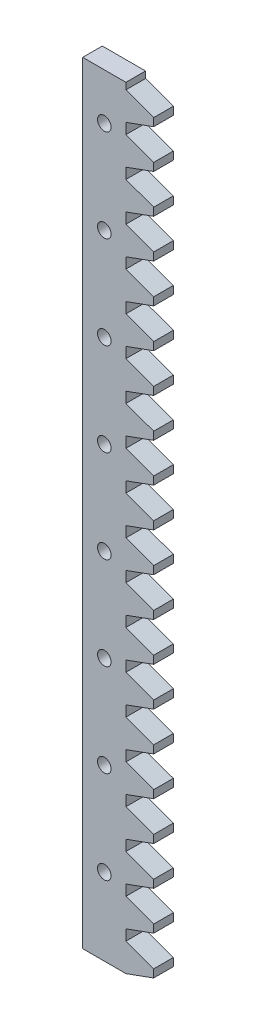
SolidWorks part; units mm, degrees
ref_plane "Front Plane" through (0, 0, 0) normal (0, 0, 1) x (1, 0, 0)
ref_plane "Top Plane" through (0, 0, 0) normal (0, 1, 0) x (1, 0, 0)
ref_plane "Right Plane" through (0, 0, 0) normal (1, 0, 0) x (0, 0, -1)
sketch "Sketch2" plane through (0, 0, 0) normal (0, 0, 1) x (1, 0, 0)
  line L0 (0, -62.5) -> (0, 62.5) construction
  line L1 (-3.5, -62.5) -> (3.5, -62.5) construction
  line L2 (-3.5, -62.5) -> (-3.5, 62.5) construction
  line L3 (-3.5, 62.5) -> (3.5, 62.5) construction
  line L4 (3.5, -62.5) -> (3.5, 62.5) construction
  line L5 (-3.5, -62.5) -> (3.5, 62.5) construction
  line L6 (-3.5, 62.5) -> (3.5, -62.5) construction
  line L8 (5.5085, -61.769) -> (8, -60.8621)
  line L9 (8, -60.8621) -> (8, -59.5784)
  line L10 (8, -59.5784) -> (3.5, -57.9406)
  line L11 (3.5, -57.9406) -> (3.5, -56.2168)
  line L12 (3.5, -56.2168) -> (8, -54.5789)
  line L13 (8, -54.5789) -> (8, -53.2952)
  line L14 (8, -53.2952) -> (3.5, -51.6574)
  line L15 (3.5, -51.6574) -> (3.5, -49.9336)
  line L16 (3.5, -49.9336) -> (8, -48.2958)
  line L17 (8, -48.2958) -> (8, -47.0121)
  line L18 (8, -47.0121) -> (3.5, -45.3742)
  line L19 (3.5, -45.3742) -> (3.5, -43.6504)
  line L20 (3.5, -43.6504) -> (8, -42.0126)
  line L21 (8, -42.0126) -> (8, -40.7289)
  line L22 (8, -40.7289) -> (3.5, -39.091)
  line L23 (3.5, -39.091) -> (3.5, -37.3673)
  line L24 (3.5, -37.3673) -> (8, -35.7294)
  line L25 (8, -35.7294) -> (8, -34.4457)
  line L26 (8, -34.4457) -> (3.5, -32.8078)
  line L27 (3.5, -32.8078) -> (3.5, -31.0841)
  line L28 (3.5, -31.0841) -> (8, -29.4462)
  line L29 (8, -29.4462) -> (8, -28.1625)
  line L30 (8, -28.1625) -> (3.5, -26.5246)
  line L31 (3.5, -26.5246) -> (3.5, -24.8009)
  line L32 (3.5, -24.8009) -> (8, -23.163)
  line L33 (8, -23.163) -> (8, -21.8793)
  line L34 (8, -21.8793) -> (3.5, -20.2414)
  line L35 (3.5, -20.2414) -> (3.5, -18.5177)
  line L36 (3.5, -18.5177) -> (8, -16.8798)
  line L37 (8, -16.8798) -> (8, -15.5961)
  line L38 (8, -15.5961) -> (3.5, -13.9583)
  line L39 (3.5, -13.9583) -> (3.5, -12.2345)
  line L40 (3.5, -12.2345) -> (8, -10.5967)
  line L41 (8, -10.5967) -> (8, -9.3129)
  line L42 (8, -9.3129) -> (3.5, -7.6751)
  line L43 (3.5, -7.6751) -> (3.5, -5.9513)
  line L44 (3.5, -5.9513) -> (8, -4.3135)
  line L45 (8, -4.3135) -> (8, -3.0298)
  line L46 (8, -3.0298) -> (3.5, -1.3919)
  line L47 (3.5, -1.3919) -> (3.5, 0.3319)
  line L48 (3.5, 0.3319) -> (8, 1.9697)
  line L49 (8, 1.9697) -> (8, 3.2534)
  line L50 (8, 3.2534) -> (3.5, 4.8913)
  line L51 (3.5, 4.8913) -> (3.5, 6.615)
  line L52 (3.5, 6.615) -> (8, 8.2529)
  line L53 (8, 8.2529) -> (8, 9.5366)
  line L54 (8, 9.5366) -> (3.5, 11.1745)
  line L55 (3.5, 11.1745) -> (3.5, 12.8982)
  line L56 (3.5, 12.8982) -> (8, 14.5361)
  line L57 (8, 14.5361) -> (8, 15.8198)
  line L58 (8, 15.8198) -> (3.5, 17.4577)
  line L59 (3.5, 17.4577) -> (3.5, 19.1814)
  line L60 (3.5, 19.1814) -> (8, 20.8193)
  line L61 (8, 20.8193) -> (8, 22.103)
  line L62 (8, 22.103) -> (3.5, 23.7409)
  line L63 (3.5, 23.7409) -> (3.5, 25.4646)
  line L64 (3.5, 25.4646) -> (8, 27.1025)
  line L65 (8, 27.1025) -> (8, 28.3862)
  line L66 (8, 28.3862) -> (3.5, 30.024)
  line L67 (3.5, 30.024) -> (3.5, 31.7478)
  line L68 (3.5, 31.7478) -> (8, 33.3856)
  line L69 (8, 33.3856) -> (8, 34.6694)
  line L70 (8, 34.6694) -> (3.5, 36.3072)
  line L71 (3.5, 36.3072) -> (3.5, 38.031)
  line L72 (3.5, 38.031) -> (8, 39.6688)
  line L73 (8, 39.6688) -> (8, 40.9525)
  line L74 (8, 40.9525) -> (3.5, 42.5904)
  line L75 (3.5, 42.5904) -> (3.5, 44.3142)
  line L76 (3.5, 44.3142) -> (8, 45.952)
  line L77 (8, 45.952) -> (8, 47.2357)
  line L78 (8, 47.2357) -> (3.5, 48.8736)
  line L79 (3.5, 48.8736) -> (3.5, 50.5973)
  line L80 (3.5, 50.5973) -> (8, 52.2352)
  line L81 (8, 52.2352) -> (8, 53.5189)
  line L82 (8, 53.5189) -> (3.5, 55.1568)
  line L83 (3.5, 55.1568) -> (3.5, 56.8805)
  line L84 (3.5, 56.8805) -> (8, 58.5184)
  line L85 (8, 58.5184) -> (8, 59.8021)
  line L86 (8, 59.8021) -> (3.5, 61.44)
  line L87 (3.5, 61.44) -> (3.5, 63.1637)
  line L88 (3.5, 63.1637) -> (8, 64.8016)
  line L89 (8, 64.8016) -> (8, 66.0853)
  line L90 (8, 66.0853) -> (3.5, 67.7231)
  line L91 (3.5, 67.7231) -> (3.5, 69.4469)
  line L92 (3.5, 69.4469) -> (8, 71.0848)
  line L93 (8, 71.0848) -> (8, 72.3685)
  line L94 (8, 72.3685) -> (3.5, 74.0063)
  line L95 (3.5, 74.0063) -> (3.5, 75.7301)
  line L96 (3.5, 75.7301) -> (8, 77.3679)
  line L97 (8, 77.3679) -> (8, 78.6517)
  line L98 (8, 78.6517) -> (3.5, 80.2895)
  line L99 (3.5, 80.2895) -> (3.5, 82.0133)
  line L100 (3.5, 82.0133) -> (8, 83.6511)
  line L101 (8, 83.6511) -> (8, 84.9348)
  line L102 (8, 84.9348) -> (3.5, 86.5727)
  line L103 (3.5, 86.5727) -> (3.5, 88.2964)
  line L104 (3.5, 88.2964) -> (8, 89.9343)
  line L105 (8, 89.9343) -> (8, 91.218)
  line L106 (8, 91.218) -> (3.5, 92.8559)
  line L107 (3.5, 92.8559) -> (3.5, 94.5796)
  line L108 (3.5, 94.5796) -> (8, 96.2175)
  line L109 (8, 96.2175) -> (8, 97.5012)
  line L110 (8, 97.5012) -> (3.5, 99.1391)
  line L111 (3.5, 99.1391) -> (3.5, 100.8628)
  line L112 (3.5, 100.8628) -> (8, 102.5007)
  line L113 (8, 102.5007) -> (8, 103.7844)
  line L114 (8, 103.7844) -> (3.5, 105.4223)
  line L115 (3.5, 105.4223) -> (3.5, 107.146)
  line L116 (3.5, 107.146) -> (8, 108.7839)
  line L117 (8, 108.7839) -> (8, 110.0676)
  line L118 (8, 110.0676) -> (3.5, 111.7054)
  line L119 (3.5, 111.7054) -> (3.5, 113.4292)
  line L120 (3.5, 113.4292) -> (8, 115.0671)
  line L121 (8, 115.0671) -> (8, 116.3508)
  line L122 (8, 116.3508) -> (3.5, 117.9886)
  line L123 (3.5, 117.9886) -> (3.5, 119.7124)
  line L124 (3.5, 119.7124) -> (8, 121.3502)
  line L125 (8, 121.3502) -> (8, 122.634)
  line L126 (8, 122.634) -> (3.5, 124.2718)
  line L127 (3.5, 124.2718) -> (3.5, 125.9956)
  line L128 (3.5, 125.9956) -> (8, 127.6334)
  line L129 (8, 127.6334) -> (8, 128.9171)
  line L130 (8, 128.9171) -> (3.5, 130.555)
  line L131 (3.5, 130.555) -> (3.5, 132.2787)
  line L132 (3.5, 132.2787) -> (8, 133.9166)
  line L133 (8, 133.9166) -> (8, 135.2003)
  line L134 (8, 135.2003) -> (3.5, 136.8382)
  line L135 (3.5, 136.8382) -> (3.5, 138.5619)
  line L136 (3.5, 138.5619) -> (8, 140.1998)
  line L137 (8, 140.1998) -> (8, 141.4835)
  line L138 (8, 141.4835) -> (3.5, 143.1214)
  line L139 (3.5, 143.1214) -> (3.5, 144.8451)
  line L140 (3.5, 144.8451) -> (8, 146.483)
  line L141 (8, 146.483) -> (8, 147.7667)
  line L142 (8, 147.7667) -> (3.5, 149.4046)
  line L143 (3.5, 149.4046) -> (3.5, 151.1283)
  line L144 (3.5, 151.1283) -> (8, 152.7662)
  line L145 (8, 152.7662) -> (8, 154.0499)
  line L146 (8, 154.0499) -> (3.5, 155.6877)
  line L147 (3.5, 155.6877) -> (3.5, 157.4115)
  line L148 (3.5, 157.4115) -> (8, 159.0494)
  line L149 (8, 159.0494) -> (8, 160.3331)
  line L150 (8, 160.3331) -> (3.5, 161.9709)
  line L151 (3.5, 161.9709) -> (3.5, 163.6947)
  line L152 (3.5, 163.6947) -> (8, 165.3325)
  line L153 (8, 165.3325) -> (8, 166.6162)
  line L154 (8, 166.6162) -> (3.5, 168.2541)
  line L155 (3.5, 168.2541) -> (3.5, 169.9779)
  line L156 (3.5, 169.9779) -> (8, 171.6157)
  line L157 (8, 171.6157) -> (8, 172.8994)
  line L158 (8, 172.8994) -> (3.5, 174.5373)
  line L159 (3.5, 174.5373) -> (3.5, 176.261)
  line L160 (3.5, 176.261) -> (8, 177.8989)
  line L161 (8, 177.8989) -> (8, 179.1826)
  line L162 (8, 179.1826) -> (3.5, 180.8205)
  line L163 (3.5, 180.8205) -> (3.5, 182.5442)
  line L164 (3.5, 182.5442) -> (8, 184.1821)
  line L165 (8, 184.1821) -> (8, 185.4658)
  line L166 (8, 185.4658) -> (3.5, 187.1037)
  line L167 (3.5, 187.1037) -> (3.5, 188.8274)
  line L168 (3.5, 188.8274) -> (8, 190.4653)
  line L169 (8, 190.4653) -> (8, 191.749)
  line L170 (8, 191.749) -> (3.5, 193.3869)
  line L171 (3.5, 193.3869) -> (3.5, 195.1106)
  line L172 (3.5, 195.1106) -> (8, 196.7485)
  line L173 (8, 196.7485) -> (8, 198.0322)
  line L174 (8, 198.0322) -> (3.5, 199.67)
  line L175 (3.5, 199.67) -> (3.5, 201.3938)
  line L176 (3.5, 201.3938) -> (8, 203.0316)
  line L177 (8, 203.0316) -> (8, 204.3154)
  line L178 (8, 204.3154) -> (3.5, 205.9532)
  line L179 (3.5, 205.9532) -> (3.5, 207.677)
  line L180 (3.5, 207.677) -> (8, 209.3148)
  line L181 (8, 209.3148) -> (8, 210.5985)
  line L182 (8, 210.5985) -> (3.5, 212.2364)
  line L183 (3.5, 212.2364) -> (3.5, 213.9602)
  line L184 (3.5, 213.9602) -> (8, 215.598)
  line L185 (8, 215.598) -> (8, 216.8817)
  line L186 (8, 216.8817) -> (3.5, 218.5196)
  line L187 (3.5, 218.5196) -> (3.5, 220.2433)
  line L188 (3.5, 220.2433) -> (8, 221.8812)
  line L189 (8, 221.8812) -> (8, 223.1649)
  line L190 (8, 223.1649) -> (3.5, 224.8028)
  line L191 (3.5, 224.8028) -> (3.5, 226.5265)
  line L192 (3.5, 226.5265) -> (8, 228.1644)
  line L193 (8, 228.1644) -> (8, 229.4481)
  line L194 (8, 229.4481) -> (3.5, 231.086)
  line L195 (3.5, 231.086) -> (3.5, 232.8097)
  line L196 (3.5, 232.8097) -> (8, 234.4476)
  line L197 (8, 234.4476) -> (8, 235.7313)
  line L198 (8, 235.7313) -> (3.5, 237.3692)
  line L199 (3.5, 237.3692) -> (3.5, 238.231)
  line L200 (5.5085, -61.769) -> (3.5, -62.5)
  line L202 (3.5, -62.5) -> (-3.5, -62.5)
  line L203 (-3.5, -62.5) -> (-3.5, 62.5)
  line L204 (-3.5, 62.5) -> (3.5, 62.5)
  circle A1 centre (0, 55) radius 1.1
  circle A2 centre (0, 40) radius 1.1
  circle A3 centre (0, 25) radius 1.1
  circle A4 centre (0, 10) radius 1.1
  circle A5 centre (0, -5) radius 1.1
  circle A6 centre (0, -20) radius 1.1
  circle A7 centre (0, -35) radius 1.1
  circle A8 centre (0, -50) radius 1.1
  circle A9 centre (0, 55) radius 1.625
  circle A10 centre (0, 40) radius 1.625
  circle A11 centre (0, 25) radius 1.625
  circle A12 centre (0, 10) radius 1.625
  circle A13 centre (0, -5) radius 1.625
  circle A14 centre (0, -20) radius 1.625
  circle A15 centre (0, -35) radius 1.625
  circle A16 centre (0, -50) radius 1.625
  point P0 (0, 0)
  dimension "D3" = 2.2
  dimension "D7" = 3.25
  dimension "D1" = 7
  dimension "D2" = 125
  dimension "D4" = 7.5
  dimension "D6" = 15
  dimension "D5" = 8
  dimension "D8" = 8
extrude "Boss-Extrude1" add sketch "Sketch2" along normal blind 3.175 contours L204 L203 L202 L200 L8 L9 L10 L11 L12 L13 L14 L15 L16 L17 L18 L19 L20 L21 L22 L23 L24 L25 L26 L27 L28 L29 L30 L31 L32 L33 L34 L35 L36 L37 L38 L39 L40 L41 L42 L43 L44 L45 L46 L47 L48 L49 L50 L51 L52 L53 L54 | A9 A1 | A10 A2 | A11 A3 | A12 A4 | A13 A5 | A14 A6 | A15 A7 | A16 A8 region at (1.3078, -0.2849, 0) region at (-1.579, 55, 0) region at (-1.579, 40, 0) region at (-1.579, 25, 0) region at (-1.579, 10, 0) region at (-1.579, -5, 0) region at (-1.579, -20, 0) region at (-1.579, -35, 0) region at (-1.579, -50, 0)
